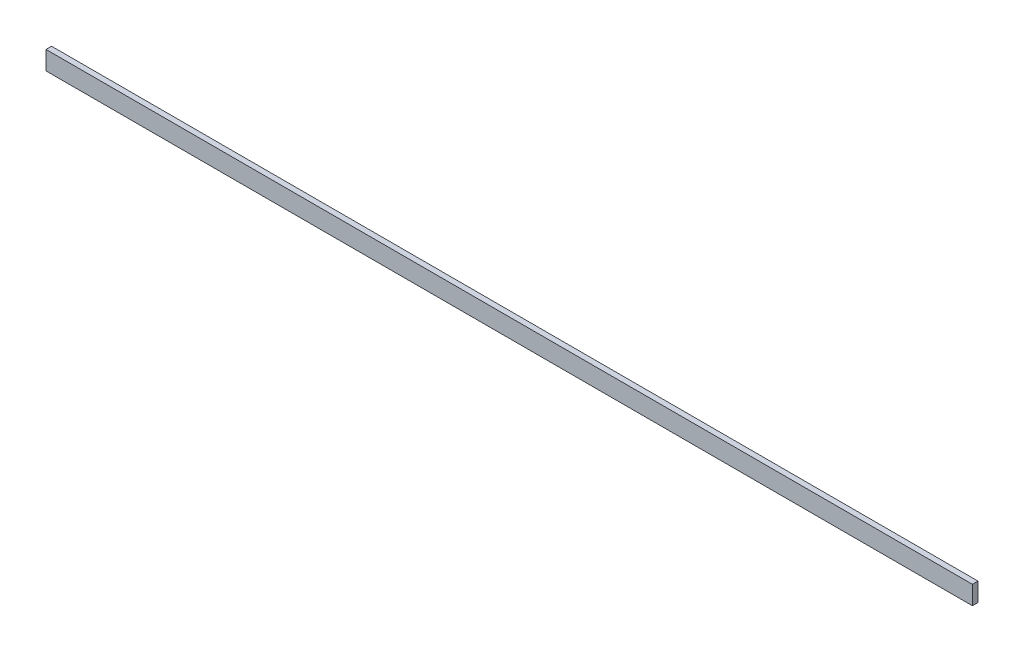
SolidWorks part; units mm, degrees
ref_plane "Ön Düzlem" through (0, 0, 0) normal (0, 0, 1) x (1, 0, 0)
ref_plane "Üst Düzlem" through (0, 0, 0) normal (0, 1, 0) x (1, 0, 0)
ref_plane "Sağ Düzlem" through (0, 0, 0) normal (1, 0, 0) x (0, 0, -1)
sketch "Çizim1" plane through (0, 0, 0) normal (0, 0, 1) x (1, 0, 0)
  line L1 (0, 0) -> (2490, 0)
  line L2 (0, 0) -> (0, -50)
  line L3 (0, -50) -> (2490, -50)
  line L4 (2490, 0) -> (2490, -50)
  dimension "D1" = 50
  dimension "D2" = 2490
base flange "Taban-Flanş1" sketch "Çizim1" thickness 15 reverse thickness direction no parameters "D1"=2.5
sketch "Büküm-Çizgileri1" [suppressed] plane through (0, 0, 0) normal (0, 1, 0) x (1, 0, 0)
sketch "Sınırlandırma-Kutusu1" [suppressed] plane through (0, 0, 0) normal (0, 1, 0) x (1, 0, 0)
sheet metal parameters "Sac-Levha1" thickness 15 parameters "D1"=2.5
flat pattern "Düz-Çoğaltma1" [suppressed]
sketch "Büküm-Çizgileri2" plane through (0, 0, 0) normal (0, 1, 0) x (1, 0, 0)
sketch3d "Sınırlandırma-Kutusu2" [suppressed]
  line L0 (0, -50, 0) -> (-2490, -50, 0) construction
  line L1 (0, 0, 0) -> (-2490, 0, 0) construction
  line L2 (0, -50, 0) -> (0, 0, 0) construction
  line L3 (-2490, -50, 0) -> (-2490, 0, 0) construction
